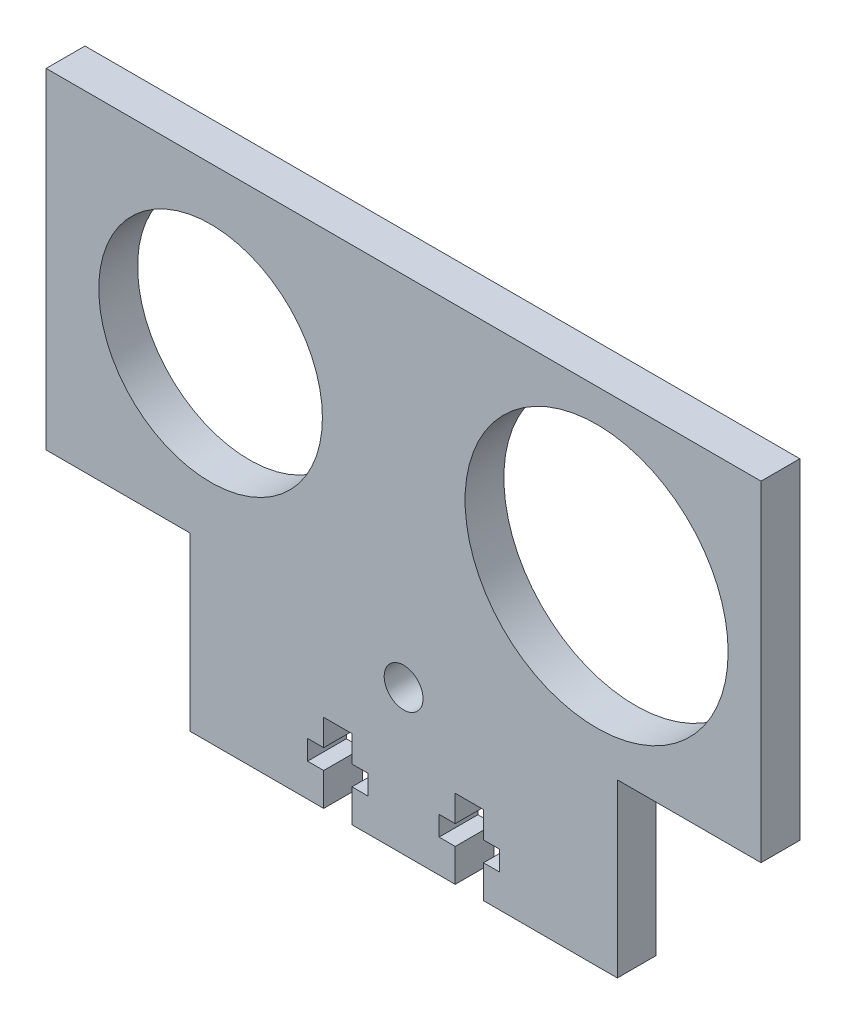
SolidWorks part; units mm, degrees
ref_plane "Front Plane" through (0, 0, 0) normal (0, 0, 1) x (1, 0, 0)
ref_plane "Top Plane" through (0, 0, 0) normal (0, 1, 0) x (1, 0, 0)
ref_plane "Right Plane" through (0, 0, 0) normal (1, 0, 0) x (0, 0, -1)
sketch "Sketch1" plane through (0, 0, 0) normal (0, 0, 1) x (1, 0, 0)
  line L0 (0, 0) -> (-29.3449, 29.3449) construction
  line L1 (0, 0) -> (0, 54.3449) construction
  line L2 (-32.5, 4.1) -> (-32.5, -22)
  line L3 (-32.5, -22) -> (32.5, -22)
  line L4 (32.5, 4.1) -> (54.3449, 4.1)
  line L5 (0, 0) -> (0, -22) construction
  line L6 (54.3449, 4.1) -> (54.3449, 54.3449)
  line L7 (0, 0) -> (29.3449, 29.3449) construction
  line L10 (-32.5, 4.1) -> (-54.3449, 4.1)
  line L11 (-54.3449, 4.1) -> (-54.3449, 54.3449)
  line L12 (-54.3449, 54.3449) -> (54.3449, 54.3449)
  line L13 (32.5, 4.1) -> (32.5, -22)
  circle A0 centre (0, 0) radius 2.95
  circle A1 centre (-29.3449, 29.3449) radius 17
  circle A2 centre (29.3449, 29.3449) radius 20
  point P16 (0, 54.3449)
  dimension "D1" = 5.9
  dimension "D9" = 34
  dimension "D10" = 40
  dimension "D2" = 41.5
  dimension "D4" = 45
  dimension "D5" = 22
  dimension "D6" = 65
  dimension "D7" = 26.1
  dimension "D8" = 25
  dimension "D3" = 25
  dimension "D11" = 45
extrude "Boss-Extrude1" add sketch "Sketch1" along normal blind 5.9
sketch "Sketch3" plane through (0, 0, 5.9) normal (0, 0, 1) x (1, 0, 0)
  line L0 (-32.5, -22) -> (32.5, -22) construction
  line L1 (-12.15, -22) -> (-7.85, -22)
  line L2 (-12.15, -22) -> (-12.15, -17)
  line L3 (-12.15, -10) -> (-7.85, -10)
  line L4 (-7.85, -22) -> (-7.85, -17)
  line L5 (0, 0) -> (0, -22) construction
  line L6 (-7.85, -14) -> (-5.4, -14)
  line L7 (-14.6, -14) -> (-12.15, -14)
  line L8 (-14.6, -14) -> (-14.6, -17)
  line L9 (-14.6, -17) -> (-12.15, -17)
  line L10 (-5.4, -14) -> (-5.4, -17)
  line L11 (-12.15, -14) -> (-12.15, -10)
  line L12 (-7.85, -17) -> (-5.4, -17)
  line L13 (-7.85, -14) -> (-7.85, -10)
  line L14 (7.85, -14) -> (7.85, -10)
  line L15 (7.85, -17) -> (5.4, -17)
  line L16 (12.15, -14) -> (12.15, -10)
  line L17 (5.4, -14) -> (5.4, -17)
  line L18 (14.6, -17) -> (12.15, -17)
  line L19 (14.6, -14) -> (14.6, -17)
  line L20 (14.6, -14) -> (12.15, -14)
  line L21 (7.85, -14) -> (5.4, -14)
  line L22 (7.85, -22) -> (7.85, -17)
  line L23 (12.15, -10) -> (7.85, -10)
  line L24 (12.15, -22) -> (12.15, -17)
  line L25 (12.15, -22) -> (7.85, -22)
  point P6 (-10, -10)
  point P18 (-13.375, -17)
  dimension "D1" = 4.3
  dimension "D2" = 10
  dimension "D3" = 12
  dimension "D4" = 9.2
  dimension "D5" = 3
  dimension "D6" = 5
extrude "Cut-Extrude2" cut sketch "Sketch3" against normal through all
equation "\"smallPulleyTeeth\"= 15"
equation "\"largePulleyTeeth\"= 30"
equation "\"eighthThick\"= 2.9mm"
equation "\"sixteenthThick\" = 1.7mm"
equation "\"quarterThick\"=5.9mm"
equation "\"OD\" = 145mm"
equation "\"puckAngle\" = 60.5deg"
equation "\"puckDiam\" = 76.5mm"
equation "\"axlePress\" = 5.9mm"
equation "\"D1@Sketch1\"=\"axlePress\""
equation "\"D1@Boss-Extrude1\"=\"quarterThick\""
equation "\"press\" = 0.2mm"
equation "\"wheelClear\" = 0.3mm"
equation "\"10-32clear\" = 4.5mm"
equation "\"D1@Sketch3\"=\"10-32clear\" - \"press\""
equation "\"6-32clear\" = 3.3mm"
equation "\"8-32clear\" = 4.0mm"
equation "\"wheelHeight\" = 22mm"
equation "\"D5@Sketch1\"=\"wheelHeight\""
equation "\"D7@Sketch1\"=\"eighthThick\"*9"
equation "\"4-40clear\" = 2.55mm"
equation "\"wheelWell\" = 65mm"
equation "\"D6@Sketch1\"=\"wheelWell\""
